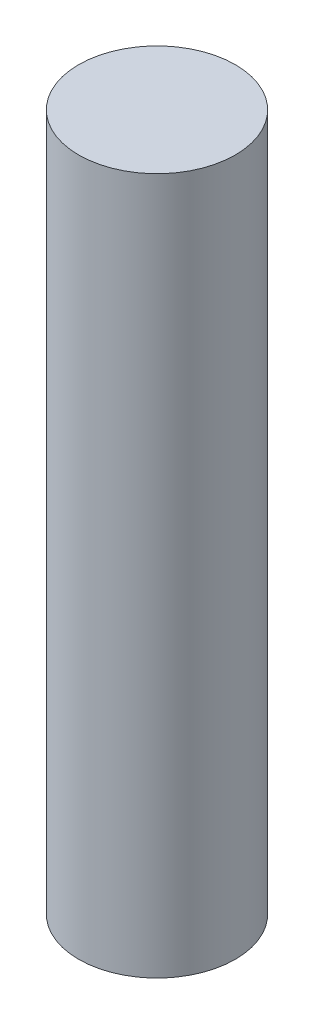
SolidWorks part; units mm, degrees
ref_plane "Front Plane" through (0, 0, 0) normal (0, 0, 1) x (1, 0, 0)
ref_plane "Top Plane" through (0, 0, 0) normal (0, 1, 0) x (1, 0, 0)
ref_plane "Right Plane" through (0, 0, 0) normal (1, 0, 0) x (0, 0, -1)
sketch "Sketch1" plane through (0, 0, 0) normal (0, 1, 0) x (1, 0, 0)
  circle A0 centre (0, 0) radius 12.7
  dimension "D1" = 25.4
extrude "Boss-Extrude1" add sketch "Sketch1" along normal blind 113
equation "\"carbon_fiber_tube_diam\"= 1in, 25.4mm"
equation "\"clip_tube_diam\"= 6mm"
equation "\"middle_tube_len\"= 500mm"
equation "\"horizontal_pipe_spacing\"= 260mm"
equation "\"D1@Sketch1\"=\"carbon_fiber_tube_diam\""
